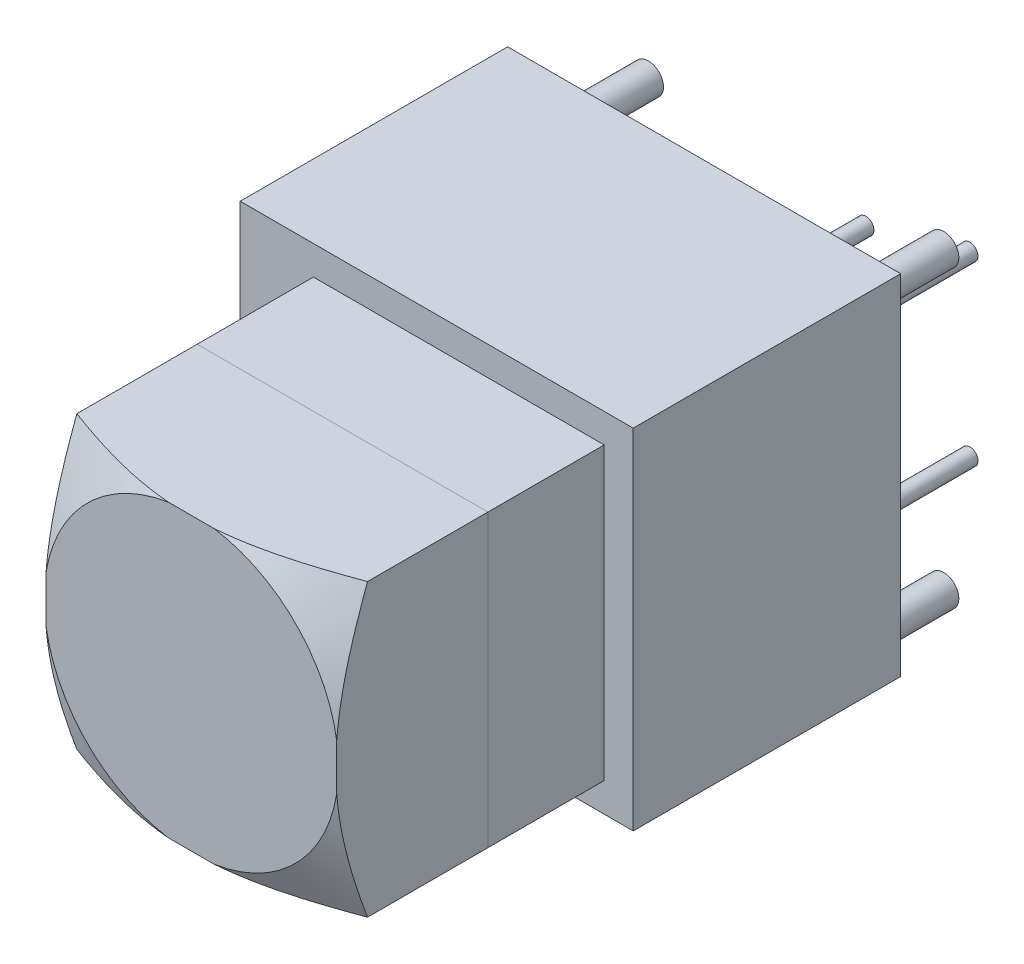
SolidWorks part; units mm, degrees
ref_plane "Front Plane" through (0, 0, 0) normal (0, 0, 1) x (1, 0, 0)
ref_plane "Top Plane" through (0, 0, 0) normal (0, 1, 0) x (1, 0, 0)
ref_plane "Right Plane" through (0, 0, 0) normal (1, 0, 0) x (0, 0, -1)
sketch "Sketch1" plane through (0, 0, 0) normal (0, 0, 1) x (1, 0, 0)
  line L1 (-8.45, -7.5) -> (8.45, -7.5)
  line L2 (-8.45, -7.5) -> (-8.45, 7.5)
  line L3 (-8.45, 7.5) -> (8.45, 7.5)
  line L4 (8.45, -7.5) -> (8.45, 7.5)
  line L5 (-8.45, -7.5) -> (8.45, 7.5) construction
  line L6 (-8.45, 7.5) -> (8.45, -7.5) construction
  point P0 (0, 0)
  dimension "D1" = 15
  dimension "D2" = 16.9
extrude "Boss-Extrude1" add sketch "Sketch1" along normal blind 11.5
sketch "Sketch3" plane through (0, 0, 0) normal (0, 0, -1) x (-1, 0, 0)
  line L0 (-8.45, 0) -> (-5.425, 0) construction
  line L1 (-7.3, 6.35) -> (5.4, 6.35) construction
  line L2 (-7.3, 6.35) -> (-7.3, -6.35) construction
  line L3 (-7.3, -6.35) -> (5.4, -6.35) construction
  line L4 (5.4, 6.35) -> (5.4, -6.35) construction
  line L5 (-8.45, -7.5) -> (-8.45, 7.5) construction
  line L6 (-7.3, 0) -> (-4.8615, 0) construction
  line L7 (-7.3, 6.35) -> (-7.3, 7.5) construction
  line L9 (-8.45, 7.5) -> (8.45, 7.5) construction
  line L10 (-5.425, -3.81) -> (-5.425, 3.81) construction
  line L11 (-5.425, 0) -> (-0.95, 0) construction
  line L12 (-0.95, 2.54) -> (-0.95, -2.54) construction
  line L13 (-7.3, 6.35) -> (-8.45, 6.35) construction
  circle A0 centre (-7.3, -6.35) radius 0.65
  circle A1 centre (-7.3, 6.35) radius 0.65
  circle A2 centre (5.4, 6.35) radius 0.65
  circle A3 centre (5.4, -6.35) radius 0.65
  circle A4 centre (-5.425, 3.81) radius 0.35
  circle A5 centre (-0.95, 2.54) radius 0.35
  circle A6 centre (-0.95, 0) radius 0.35
  circle A7 centre (-0.95, -2.54) radius 0.35
  circle A8 centre (-5.425, -3.81) radius 0.35
  point P11 (0, 0)
  point P17 (-0.95, 2.8582)
  point P18 (-0.95, 0)
  point P23 (-5.425, 0)
  dimension "D1" = 1.3
  dimension "D4" = 0.7
  dimension "D2" = 12.7
  dimension "D3" = 12.7
  dimension "D5" = 1.875
  dimension "D6" = 6.35
  dimension "D7" = 2.54
  dimension "D8" = 7.62
extrude "Boss-Extrude2" add sketch "Sketch3" along normal blind 3 contours A2 | A3 | A0 | A1 region at (7.3, -6.35, 0) region at (-5.4, 6.35, 0) region at (-5.4, -6.35, 0)
extrude "Boss-Extrude3" add sketch "Sketch3<3>" along normal blind 6 contours A4 | A5 | A7 | A8 | A6 region at (5.425, 3.81, 0) region at (0.95, 2.54, 0) region at (0.95, -2.54, 0) region at (5.425, -3.81, 0)
sketch "Sketch3<3>" plane through (0, 0, 0) normal (0, 0, -1) x (-1, 0, 0) same geometry as "Sketch3"
sketch "Sketch6" plane through (0, 0, 11.5) normal (0, 0, 1) x (1, 0, 0)
  line L0 (8.45, 0) -> (0.95, 0) construction
  line L1 (8.45, -7.5) -> (8.45, 7.5) construction
  line L2 (7.2, 6.25) -> (8.45, 7.5) construction
  line L3 (7.2, 6.25) -> (-5.3, 6.25)
  line L4 (7.2, 6.25) -> (7.2, -6.25)
  line L5 (7.2, -6.25) -> (-5.3, -6.25)
  line L6 (-5.3, 6.25) -> (-5.3, -6.25)
  line L7 (7.2, 6.25) -> (-5.3, -6.25) construction
  line L8 (7.2, -6.25) -> (-5.3, 6.25) construction
  line L9 (8.45, 7.5) -> (-8.45, 7.5) construction
  dimension "D1" = 12.5
  dimension "D2" = 45
extrude "Boss-Extrude4" add sketch "Sketch6" along normal blind 5 contours L4 L5 L6 L3
sketch "Sketch7" plane through (0, 0, 16.5) normal (0, 0, 1) x (1, 0, 0)
  line L1 (7.2, -6.25) -> (-5.3, -6.25)
  line L2 (7.2, -6.25) -> (7.2, 6.25)
  line L3 (7.2, 6.25) -> (-5.3, 6.25)
  line L4 (-5.3, -6.25) -> (-5.3, 6.25)
extrude "Boss-Extrude5" add sketch "Sketch7" along normal blind 6.5 separate body
ref_plane "Plane1" through (0, 0, 0) normal (0, 1, 0) x (1, 0, 0)
ref_plane "Plane2" through (0.95, 0, 0) normal (-1, 0, 0) x (0, 0, 1)
ref_axis "Axis1" through (0.95, 0, 16.175) along (0, 0, 1)
sketch "Sketch9" plane through (0, 0, 0) normal (0, 1, 0) x (1, 0, 0)
  line L0 (-5.3533, -23.0129) -> (-10.0189, -20.5483)
  line L1 (-10.0189, -20.5483) -> (-10.619, -23.7567)
  line L2 (-10.619, -23.7567) -> (-5.3533, -23.0129)
  point P2 (-10.0189, -20.5483)
revolve "Cut-Revolve1" cut sketch "Sketch9" angle 360 about axis through (0.95, 0, 16.175) along (0, 0, 1)
